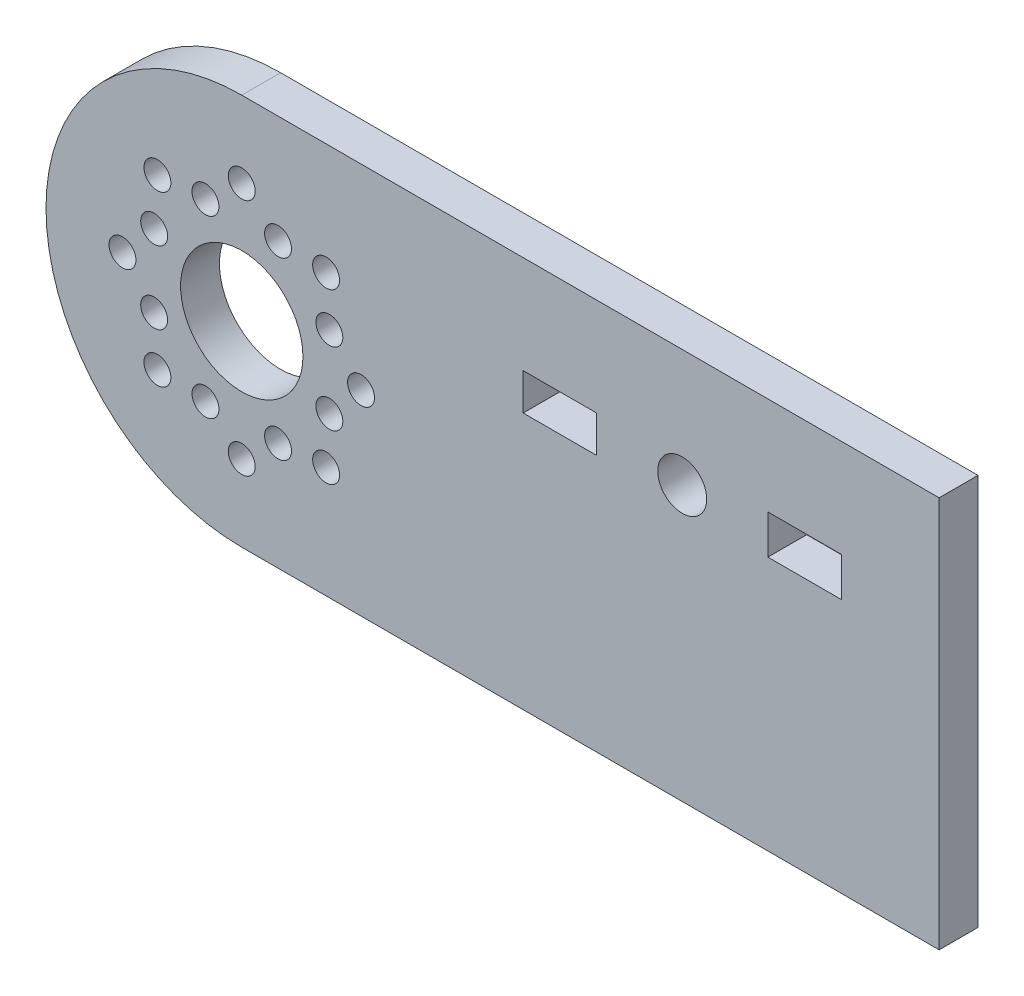
SolidWorks part; units mm, degrees
ref_plane "Front Plane" through (0, 0, 0) normal (0, 0, 1) x (1, 0, 0)
ref_plane "Top Plane" through (0, 0, 0) normal (0, 1, 0) x (1, 0, 0)
ref_plane "Right Plane" through (0, 0, 0) normal (1, 0, 0) x (0, 0, -1)
sketch "Sketch1" plane through (0, 0, 0) normal (0, 0, 1) x (1, 0, 0)
  line L1 (19, 0) -> (76, 0)
  line L2 (42, 24) -> (48, 24)
  line L3 (19, 32) -> (76, 32)
  line L4 (76, 0) -> (76, 32)
  line L5 (42, 24) -> (42, 21)
  line L6 (42, 21) -> (48, 21)
  line L7 (48, 24) -> (48, 21)
  line L8 (62, 24) -> (68, 24)
  line L9 (62, 24) -> (62, 20.7996)
  line L10 (62, 20.7996) -> (68, 20.7996)
  line L11 (68, 24) -> (68, 20.7996)
  arc A0 (19, 32) -> (19, 0) centre (19, 16) ccw
  circle A1 centre (25.8943, 22.8943) radius 1.1
  circle A2 centre (19, 25.75) radius 1.1
  circle A3 centre (28.75, 16) radius 1.1
  circle A4 centre (25.8943, 9.1057) radius 1.1
  circle A5 centre (19, 6.25) radius 1.1
  circle A6 centre (12.1057, 9.1057) radius 1.1
  circle A7 centre (9.25, 16) radius 1.1
  circle A8 centre (12.1057, 22.8943) radius 1.1
  circle A9 centre (19, 16) radius 5
  circle A10 centre (26.1601, 18.9658) radius 1.1
  circle A11 centre (21.9658, 23.1601) radius 1.1
  circle A12 centre (26.1601, 13.0342) radius 1.1
  circle A13 centre (21.9658, 8.8399) radius 1.1
  circle A14 centre (16.0342, 8.8399) radius 1.1
  circle A15 centre (11.8399, 13.0342) radius 1.1
  circle A16 centre (11.8399, 18.9658) radius 1.1
  circle A17 centre (16.0342, 23.1601) radius 1.1
  circle A18 centre (55, 22.4) radius 2
  point P24 (19, 16)
  point P42 (19, 16)
  dimension "D3" = 19
  dimension "D6" = 2.2
  dimension "D7" = 10
  dimension "D8" = 7.75
  dimension "D10" = 2.2
  dimension "D22" = 1.6
  dimension "D23" = 4
  dimension "D1" = 32
  dimension "D2" = 57
  dimension "D4" = 9.75
  dimension "D5" = 8
  dimension "D9" = 22.5
  dimension "D12" = 11.8399
  dimension "D13" = 16.0342
  dimension "D14" = 6
  dimension "D15" = 6
  dimension "D16" = 26
  dimension "D17" = 3
  dimension "D18" = 3.2004
  dimension "D19" = 8
  dimension "D20" = 8
  dimension "D21" = 13
  dimension "D11" = 8
extrude "Boss-Extrude1" add sketch "Sketch1" along normal blind 3.175
